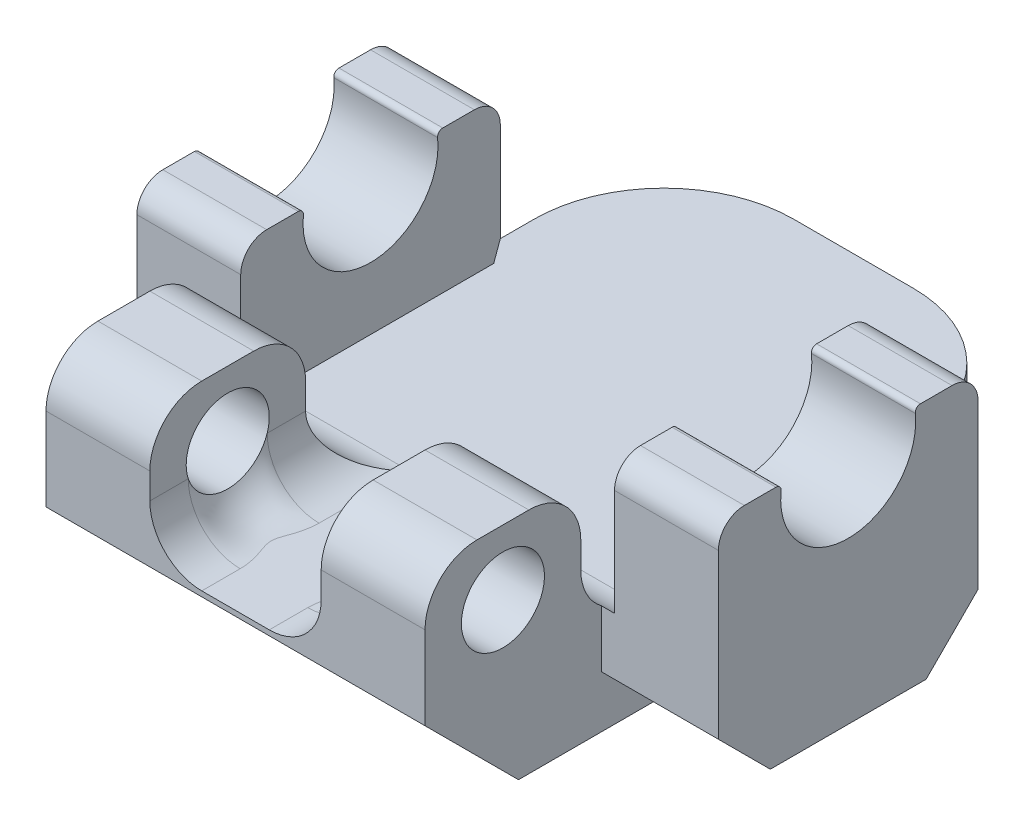
SolidWorks part; units mm, degrees
ref_plane "前视基准面" through (0, 0, 0) normal (0, 0, 1) x (1, 0, 0)
ref_plane "上视基准面" through (0, 0, 0) normal (0, 1, 0) x (1, 0, 0)
ref_plane "右视基准面" through (0, 0, 0) normal (1, 0, 0) x (0, 0, -1)
other "Configuration Table"
sketch "草图1" plane through (0, 0, 0) normal (0, 1, 0) x (1, 0, 0)
  line L1 (0, 0) -> (22.4, 0)
  line L2 (0, 0) -> (0, 26.8)
  line L3 (0, 26.8) -> (22.4, 26.8)
  line L4 (22.4, 0) -> (22.4, 26.8)
  dimension "D1" = 22.4
  dimension "D2" = 26.8
extrude "凸台-拉伸1" add sketch "草图1" along normal blind 3.8
sketch "草图2" plane through (0, 3.8, 0) normal (0, 1, 0) x (1, 0, 0)
  line L0 (0, 26.8) -> (0, 0) construction
  line L1 (0, 16.8) -> (4, 16.8)
  line L2 (0, 16.8) -> (0, 6.8)
  line L3 (0, 6.8) -> (4, 6.8)
  line L4 (4, 16.8) -> (4, 6.8)
  line L5 (22.4, 0) -> (22.4, 26.8) construction
  line L6 (22.4, 16.8) -> (18.4, 16.8)
  line L7 (22.4, 16.8) -> (22.4, 6.8)
  line L8 (22.4, 6.8) -> (18.4, 6.8)
  line L9 (18.4, 16.8) -> (18.4, 6.8)
  line L10 (22.4, 26.8) -> (0, 26.8) construction
  dimension "D1" = 10
  dimension "D2" = 10
  dimension "D3" = 4
  dimension "D4" = 4
  dimension "D5" = 10
  dimension "D6" = 10
extrude "凸台-拉伸2" add sketch "草图2" along normal blind 5.5
sketch "草图3" plane through (0, 0, 0) normal (-1, 0, 0) x (0, 0, 1)
  line L0 (-26.8, 3.8) -> (-16.8, 3.8) construction
  line L1 (-16.8, 9.3) -> (-6.8, 9.3) construction
  circle A0 centre (-11.8, 8.8) radius 2.6
  point P6 (-11.8, 9.3)
  dimension "D1" = 5.2
  dimension "D3" = 0
  dimension "D2" = 5
extrude "切除-拉伸1" cut sketch "草图3" against normal through all
sketch "草图4" plane through (0, 3.8, 0) normal (0, 1, 0) x (1, 0, 0)
  line L0 (0, 6.8) -> (0, 0) construction
  line L1 (0, 6.8) -> (3.3, 6.8)
  line L2 (0, 6.8) -> (0, 0)
  line L3 (0, 0) -> (3.3, 0)
  line L4 (3.3, 6.8) -> (3.3, 0)
  line L5 (0, 0) -> (22.4, 0) construction
  line L6 (22.4, 0) -> (22.4, 6.8) construction
  line L7 (22.4, 6.8) -> (17.9, 6.8)
  line L8 (22.4, 6.8) -> (22.4, 0)
  line L9 (22.4, 0) -> (17.9, 0)
  line L10 (17.9, 6.8) -> (17.9, 0)
  line L11 (22.4, 26.8) -> (0, 26.8) construction
  line L12 (0, 16.8) -> (3.3, 16.8)
  line L13 (0, 16.8) -> (0, 26.8)
  line L14 (0, 26.8) -> (3.3, 26.8)
  line L15 (3.3, 16.8) -> (3.3, 26.8)
  line L17 (22.4, 16.8) -> (17.9, 16.8)
  line L18 (22.4, 16.8) -> (22.4, 26.8)
  line L19 (22.4, 26.8) -> (17.9, 26.8)
  line L20 (17.9, 16.8) -> (17.9, 26.8)
  dimension "D1" = 6.8
  dimension "D2" = 6.8
  dimension "D3" = 4.5
  dimension "D4" = 3.3
  dimension "D5" = 3.3
  dimension "D6" = 4.5
extrude "切除-拉伸2" cut sketch "草图4" against normal through all
sketch "草图5" plane through (0, 3.8, 0) normal (0, 1, 0) x (1, 0, 0)
  line L0 (3.3, 0) -> (3.3, 6.8) construction
  line L1 (3.3, 6) -> (7.3, 6)
  line L2 (3.3, 6) -> (3.3, 0)
  line L3 (3.3, 0) -> (7.3, 0)
  line L4 (7.3, 6) -> (7.3, 0)
  line L5 (3.3, 0) -> (17.9, 0) construction
  line L6 (17.9, 6.8) -> (17.9, 0) construction
  line L7 (17.9, 6) -> (13.9, 6)
  line L8 (17.9, 6) -> (17.9, 0)
  line L9 (17.9, 0) -> (13.9, 0)
  line L10 (13.9, 6) -> (13.9, 0)
  dimension "D1" = 4
  dimension "D2" = 4
  dimension "D3" = 6
  dimension "D4" = 6
extrude "凸台-拉伸3" add sketch "草图5" along normal blind 5
sketch "草图6" plane through (3.3, 0, 0) normal (-1, 0, 0) x (0, 0, 1)
  circle A0 centre (-3, 6.3) radius 1.6
  dimension "D1" = 3.2
extrude "切除-拉伸3" cut sketch "草图6" against normal through all
chamfer "倒角1" distance 4.5 angle 20 1 edges at (1.65, 0, -16.8) first distance on face at (2.4333, 4.3667, -16.8)
chamfer "倒角2" distance 3 angle 45 1 edges at (1.65, 0, -6.8)
chamfer "倒角3" distance 3.6 angle 45 1 edges at (10.6, 0, 0)
sketch "草图8" plane through (0, 0, -26.8) normal (0, 0, -1) x (-1, 0, 0)
  line L0 (-17.9, 0) -> (-3.3, 0) construction
  line L1 (-17.9, 0) -> (-3.3, 0)
  line L2 (-17.9, 0) -> (-17.9, 3.8)
  line L3 (-17.9, 3.8) -> (-3.3, 3.8)
  line L4 (-3.3, 0) -> (-3.3, 3.8)
  line L5 (-17.9, 0) -> (-17.9, 3.8) construction
  line L6 (-3.3, 0) -> (-3.3, 3.8) construction
  line L7 (-17.9, 3.8) -> (-3.3, 3.8) construction
extrude "切除-拉伸4" cut sketch "草图8" against normal blind 3
fillet "圆角1" radius 2 2 edges at (7.3, 3.8, -3) (13.9, 3.8, -3)
fillet "圆角2" radius 2 4 edges at (5.3, 8.8, 0) (5.3, 8.8, -6) (15.9, 8.8, -6) (15.9, 8.8, 0)
fillet "圆角3" radius 2 2 edges at (6.3, 3.8, -6) (14.9, 3.8, -6)
fillet "圆角4" radius 1 4 edges at (20.4, 9.3, -16.8) (20.4, 9.3, -6.8) (2, 9.3, -6.8) (2, 9.3, -16.8)
fillet "圆角5" radius 0.2 4 edges at (20.4, 9.3, -14.3515) (20.4, 9.3, -9.2485) (2, 9.3, -14.3515) (2, 9.3, -9.2485)
fillet "圆角6" radius 5 2 edges at (17.9, 1.9, -23.8) (3.3, 1.9, -23.8)
chamfer "倒角4" distance 2 angle 45 2 edges at (20.15, 0, -16.8) (20.15, 0, -6.8)
